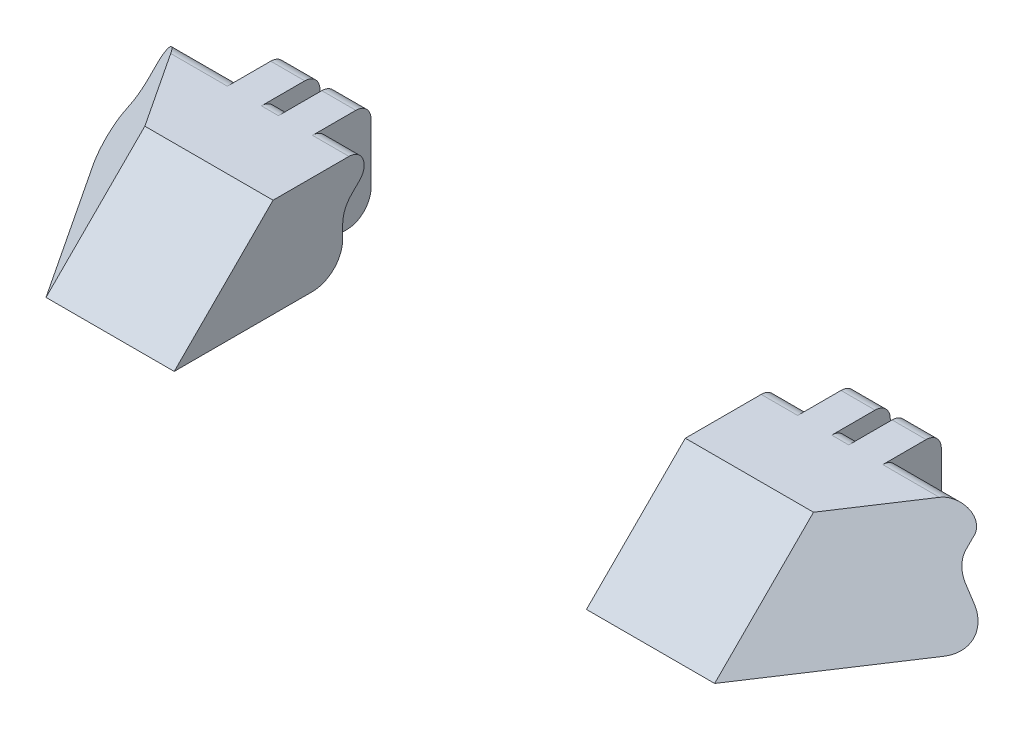
SolidWorks part; units mm, degrees
note: The reader was unsure of these and kept them because the rebuilt part matched: shared geometry of "Sketch4<2>".
ref_plane "Front Plane" through (0, 0, 0) normal (0, 0, 1) x (1, 0, 0)
ref_plane "Top Plane" through (0, 0, 0) normal (0, 1, 0) x (1, 0, 0)
ref_plane "Right Plane" through (0, 0, 0) normal (1, 0, 0) x (0, 0, -1)
sketch "Sketch1" plane through (-50.685, 0, 0) normal (-1, 0, 0) x (0, 0, 1)
  line L0 (221.3413, -23.0187) -> (200.6867, -2.3642) construction
  line L1 (175.774, -2.3642) -> (200.6867, -2.3642) construction
  line L2 (172.599, -5.5392) -> (172.599, -17.9387) construction
  line L3 (221.3413, -23.0187) -> (177.679, -23.0188) construction
  line L4 (221.3413, -23.0187) -> (200.6867, -2.3642)
  line L5 (175.774, -2.3642) -> (200.6867, -2.3642)
  line L6 (172.599, -5.5392) -> (172.599, -17.9387)
  line L7 (221.3413, -23.0187) -> (177.679, -23.0188)
  arc A0 (175.774, -2.3642) -> (172.599, -5.5392) centre (175.774, -5.5392) ccw construction
  arc A1 (172.599, -17.9387) -> (177.679, -23.0188) centre (177.679, -17.9387) ccw construction
  arc A2 (175.774, -2.3642) -> (172.599, -5.5392) centre (175.774, -5.5392) ccw
  arc A3 (172.599, -17.9387) -> (177.679, -23.0188) centre (177.679, -17.9387) ccw
  circle A4 centre (179.7902, -13.97) radius 3.175
  dimension "D1" = 6.35
extrude "Boss-Extrude1" add sketch "Sketch1" along normal blind 50.8
sketch "Sketch2" plane through (0, 99.1613, 99.1613) normal (0, 0.7071, 0.7071) x (1, 0, 0)
  line L0 (-69.85, -172.7887) -> (-69.85, -143.5787) construction
  line L1 (-101.485, -172.7887) -> (-50.685, -172.7887) construction
  line L2 (-101.485, -143.5787) -> (-50.685, -143.5787) construction
  dimension "D1" = 69.85
ref_plane "Plane1" through (-107.3081, 70.7576, 70.7576) normal (-0.7314, 0.4822, 0.4822) x (0, 0.7071, -0.7071)
sketch "Sketch3" plane through (-107.3081, 70.7576, 70.7576) normal (-0.7314, 0.4822, 0.4822) x (0, 0.7071, -0.7071)
  line L0 (-125.0327, -53.469) -> (-125.0327, -18.8235) construction
  line L1 (-172.7887, -54.924) -> (-125.0327, -54.924)
  line L2 (-172.7887, -54.924) -> (-172.7887, -9.681)
  line L3 (-172.7887, -9.681) -> (-125.0327, -9.681)
  line L4 (-125.0327, -54.924) -> (-125.0327, -9.681)
  ellipse E0 centre (-138.3226, -13.3963) end of major axis (-133.2426, -13.3963) minor radius 3.7153 (-134.7305, -10.7692) -> (-141.9147, -10.7692) ccw construction
extrude "Cut-Extrude1" cut sketch "Sketch3" along normal through all
sketch "Sketch4" plane through (-50.685, 0, 0) normal (1, 0, 0) x (0, 0, -1)
  line L1 (-184.2803, -9.4799) -> (-175.9822, -1.1817) construction
  line L2 (-200.6867, -2.3642) -> (-175.774, -2.3642) construction
  line L3 (-184.2803, -9.4799) -> (-182.5847, -7.7842)
  line L4 (-186.1402, -13.97) -> (-186.1402, -16.6688)
  line L5 (-177.679, -23.0188) -> (-221.3413, -23.0187) construction
  line L6 (-192.4902, -23.0188) -> (-172.599, -23.0188)
  line L7 (-172.599, -23.0188) -> (-172.599, -2.3642)
  line L8 (-184.8298, -2.3642) -> (-172.599, -2.3642)
  line L9 (-172.599, -5.5392) -> (-172.599, -17.9387) construction
  arc A0 (-184.2803, -9.4799) -> (-179.7902, -20.32) centre (-179.7902, -13.97) ccw construction
  arc A1 (-184.2803, -9.4799) -> (-186.1402, -13.97) centre (-179.7902, -13.97) ccw
  arc A2 (-186.1402, -16.6688) -> (-192.4902, -23.0188) centre (-192.4902, -16.6688) cw
  arc A3 (-182.5847, -7.7842) -> (-184.8298, -2.3642) centre (-184.8298, -5.5392) ccw
  dimension "D1" = 6.35
  dimension "D2" = 3.175
extrude "Cut-Extrude2" cut sketch "Sketch4" against normal up to surface (3.556 mm away) from surface at -7.112
extrude "Cut-Extrude3" cut sketch "Sketch4<2>" against normal through all from surface at -17.78
sketch "Sketch4<2>" plane through (-50.685, 0, 0) normal (1, 0, 0) x (0, 0, -1) same geometry as "Sketch4"
sketch "Sketch5" plane through (-50.685, 0, 0) normal (1, 0, 0) x (0, 0, -1)
  line L0 (-182.5847, -7.7842) -> (-184.2803, -9.4799) construction
  line L1 (-186.1402, -13.97) -> (-186.1402, -16.6688) construction
  line L2 (-182.5847, -7.7842) -> (-184.2803, -9.4799)
  line L3 (-186.1402, -13.97) -> (-186.1402, -16.6688)
  line L4 (-184.8298, -2.3642) -> (-200.6867, -2.3642)
  line L5 (-200.6867, -2.3642) -> (-221.3413, -23.0187)
  line L6 (-221.3413, -23.0187) -> (-192.4902, -23.0188)
  arc A0 (-182.5847, -7.7842) -> (-184.8298, -2.3642) centre (-184.8298, -5.5392) ccw construction
  arc A1 (-184.2803, -9.4799) -> (-186.1402, -13.97) centre (-179.7902, -13.97) ccw construction
  arc A2 (-192.4902, -23.0188) -> (-186.1402, -16.6688) centre (-192.4902, -16.6688) ccw construction
  arc A3 (-182.5847, -7.7842) -> (-184.8298, -2.3642) centre (-184.8298, -5.5392) ccw
  arc A4 (-184.2803, -9.4799) -> (-186.1402, -13.97) centre (-179.7902, -13.97) ccw
  arc A5 (-192.4902, -23.0188) -> (-186.1402, -16.6688) centre (-192.4902, -16.6688) ccw
extrude "Boss-Extrude2" add sketch "Sketch5" along normal blind 7.62
mirror "Mirror2" about plane through (0, 0, 0) normal (1, 0, 0) of bodies 105
